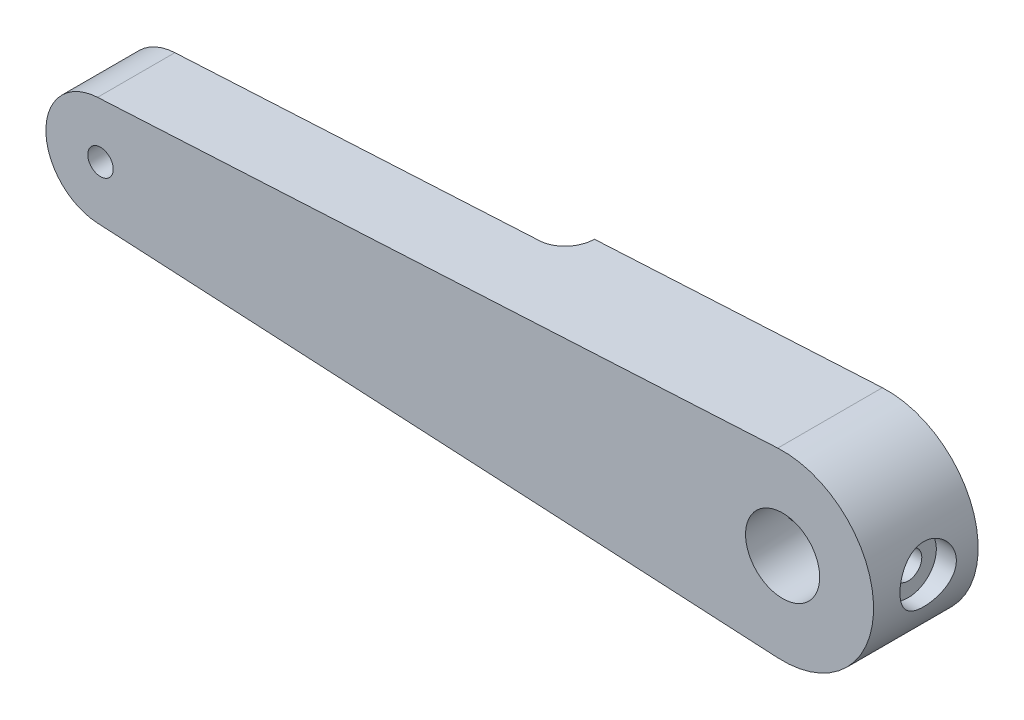
SolidWorks part; units mm, degrees
ref_plane "Спереди" through (0, 0, 0) normal (0, 0, 1) x (1, 0, 0)
ref_plane "Сверху" through (0, 0, 0) normal (0, 1, 0) x (1, 0, 0)
ref_plane "Справа" through (0, 0, 0) normal (1, 0, 0) x (0, 0, -1)
sketch "Эскиз1" plane through (0, 0, 0) normal (0, 0, 1) x (1, 0, 0)
  line L0 (32.1978, 0) -> (-42.8022, 0) construction
  line L1 (-43.1222, -5.9915) -> (31.6644, -9.9858)
  line L2 (-43.1222, 5.9915) -> (31.6644, 9.9858)
  arc A0 (-43.1222, 5.9915) -> (-43.1222, -5.9915) centre (-42.8022, 0) ccw
  arc A1 (31.6644, -9.9858) -> (31.6644, 9.9858) centre (32.1978, 0) ccw
  circle A2 centre (-42.8022, 0) radius 1.4
  circle A5 centre (32.1978, 0) radius 4.075
  dimension "D1" = 20
  dimension "D3" = 6
extrude "Бобышка-Вытянуть1" add sketch "Эскиз1" against normal offset from surface (11.5 mm away) 1
sketch "Эскиз2" plane through (0, 0, 0) normal (1, 0, 0) x (0, 0, -1)
  circle A0 centre (6, 0) radius 1.4 construction
  circle A2 centre (6, 0) radius 1.4 construction
  circle A3 centre (6, 0) radius 1.5
  circle A4 centre (6, 0) radius 3.1
  dimension "D1" = 6.2
  dimension "D2" = 3
extrude "Вырез-Вытянуть1" cut sketch "Эскиз2" along normal through all contours A3 region at (0, 0, -6)
extrude "Вырез-Вытянуть2" cut sketch "Эскиз2<3>" along normal through all from offset 40 contours A4
sketch "Эскиз2<3>" plane through (0, 0, 0) normal (1, 0, 0) x (0, 0, -1) same geometry as "Эскиз2"
sketch "Эскиз3" plane through (0, 0, 0) normal (0, 1, 0) x (1, 0, 0)
  line L1 (-57.1485, 26.3854) -> (0, 26.3854)
  line L2 (-57.1485, 26.3854) -> (-57.1485, 8.5)
  line L3 (-57.1485, 8.5) -> (-3, 8.5)
  line L4 (0, 26.3854) -> (0, 11.5)
  line L10 (-48.8022, 8.5) -> (-48.8022, 4) construction
  line L13 (-42.8022, 0) -> (-42.6715, 11.5) construction
  line L14 (-44.2022, 0) -> (-41.4022, 0) construction
  line L15 (-41.4022, 11.5) -> (-44.2022, 11.5) construction
  arc A0 (-3, 8.5) -> (0, 11.5) centre (-3, 11.5) ccw
  dimension "D1" = 3
extrude "Вырез-Вытянуть3" cut sketch "Эскиз3" against normal through all both and the other way through all
ref_axis "Ось1" through (-42.8022, 0, -8.5) along (0, 0, 1)
ref_plane "Плоскость1" through (0, 0, 6) normal (0, 0, 1) x (1, 0, 0)
sketch "Эскиз4" plane through (0, 0, -8.5) normal (0, 0, -1) x (-1, 0, 0)
  circle A0 centre (42.8022, 0) radius 3
extrude "Вырез-Вытянуть4" cut sketch "Эскиз4" against normal blind 2.5
